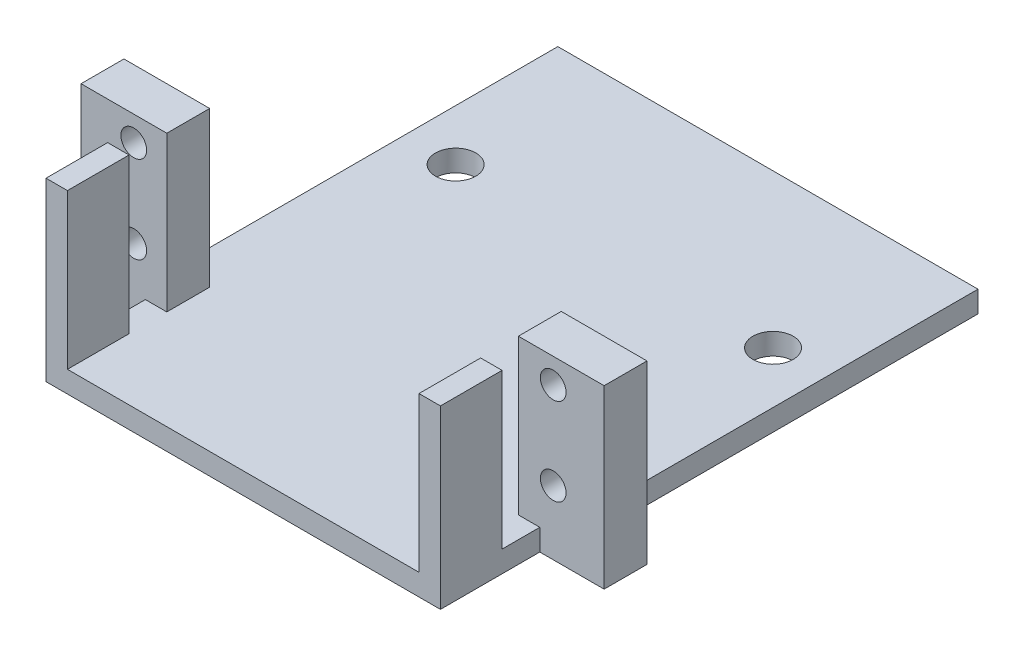
SolidWorks part; units mm, degrees
ref_plane "Front Plane" through (0, 0, 0) normal (0, 0, 1) x (1, 0, 0)
ref_plane "Top Plane" through (0, 0, 0) normal (0, 1, 0) x (1, 0, 0)
ref_plane "Right Plane" through (0, 0, 0) normal (1, 0, 0) x (0, 0, -1)
sketch "Sketch1" plane through (0, 0, 0) normal (0, 1, 0) x (1, 0, 0)
  line L1 (0, 0) -> (46, 0)
  line L2 (0, 0) -> (0, 36.614)
  line L3 (0, 36.614) -> (46, 36.614)
  line L4 (46, 0) -> (46, 36.614)
  dimension "D1" = 46
extrude "Boss-Extrude1" add sketch "Sketch1" along normal blind 2.5
sketch "Sketch2" plane through (0, 2.5, 0) normal (0, 1, 0) x (1, 0, 0)
  line L1 (0, 36.614) -> (2.5, 36.614)
  line L2 (0, 36.614) -> (0, 11.588)
  line L3 (0, 11.588) -> (2.5, 11.588)
  line L4 (2.5, 36.614) -> (2.5, 11.588)
  line L5 (0, 0) -> (2.5, 0)
  line L6 (0, 0) -> (0, 7.188)
  line L7 (0, 7.188) -> (2.5, 7.188)
  line L8 (2.5, 0) -> (2.5, 7.188)
  line L9 (46, 0) -> (43.5, 0)
  line L10 (46, 0) -> (46, 7.188)
  line L11 (46, 7.188) -> (43.5, 7.188)
  line L12 (43.5, 0) -> (43.5, 7.188)
  line L13 (46, 36.614) -> (43.5, 36.614)
  line L14 (46, 36.614) -> (46, 11.588)
  line L15 (46, 11.588) -> (43.5, 11.588)
  line L16 (43.5, 36.614) -> (43.5, 11.588)
  point P20 (44.75, 7.188)
  dimension "D1" = 2.5
  dimension "D2" = 2.5
  dimension "D3" = 2.5
  dimension "D4" = 2.5
  dimension "D5" = 7.188
  dimension "D6" = 4.4
  dimension "D7" = 7.188
  dimension "D8" = 4.4
extrude "Boss-Extrude2" add sketch "Sketch2" along normal blind 20.8351
sketch "Sketch4" plane through (0, 0, -11.588) normal (0, 0, 1) x (1, 0, 0)
  line L0 (2.5, 23.3351) -> (2.5, 2.5) construction
  line L1 (2.5, 20.5529) -> (-7.5, 20.5529)
  line L2 (2.5, 20.5529) -> (2.5, 0)
  line L3 (2.5, 0) -> (-7.5, 0)
  line L4 (-7.5, 20.5529) -> (-7.5, 0)
  line L5 (43.5, 23.3351) -> (43.5, 2.5) construction
  line L6 (43.5, 20.5529) -> (53.5, 20.5529)
  line L7 (43.5, 20.5529) -> (43.5, 0)
  line L8 (43.5, 0) -> (53.5, 0)
  line L9 (53.5, 20.5529) -> (53.5, 0)
  dimension "D1" = 10
  dimension "D2" = 10
extrude "Boss-Extrude8" add sketch "Sketch4" against normal blind 5
sketch "Sketch5" plane through (0, 0, 0) normal (-1, 0, 0) x (0, 0, 1)
  line L1 (-36.614, 23.3351) -> (-16.588, 23.3351)
  line L2 (-36.614, 23.3351) -> (-36.614, 0)
  line L3 (-36.614, 0) -> (-16.588, 0)
  line L4 (-16.588, 23.3351) -> (-16.588, 0)
extrude "Cut-Extrude1" cut sketch "Sketch5" against normal blind 100
sketch "Sketch6" plane through (0, 0, -16.588) normal (0, 0, -1) x (-1, 0, 0)
  line L0 (7.5, 0) -> (-53.5, 0) construction
  line L1 (-47.5, 2.5) -> (1.5, 2.5)
  line L2 (-47.5, 2.5) -> (-47.5, 0)
  line L3 (-47.5, 0) -> (1.5, 0)
  line L4 (1.5, 2.5) -> (1.5, 0)
  line L5 (-53.5, 0) -> (-53.5, 20.5529) construction
  line L6 (7.5, 20.5529) -> (7.5, 0) construction
  dimension "D1" = 2.5
  dimension "D2" = 6
  dimension "D3" = 6
extrude "Boss-Extrude9" add sketch "Sketch6" along normal blind 44.6018
sketch "Sketch7" plane through (0, 2.5, 0) normal (0, 1, 0) x (1, 0, 0)
  circle A0 centre (4.4582, 43.3138) radius 2.35
  circle A1 centre (41.4728, 43.3138) radius 2.35
  dimension "D1" = 4.7
  dimension "D2" = 4.7
extrude "Cut-Extrude2" cut sketch "Sketch7" against normal blind 57
sketch "Sketch8" plane through (0, 0, 0) normal (0, 0, 1) x (1, 0, 0)
sketch "Sketch9" plane through (0, 0, 0) normal (-1, 0, 0) x (0, 0, 1)
  line L1 (0, 23.3351) -> (-16.588, 23.3351)
  line L2 (0, 23.3351) -> (0, 20.5529)
  line L3 (0, 20.5529) -> (-16.588, 20.5529)
  line L4 (-16.588, 23.3351) -> (-16.588, 20.5529)
extrude "Cut-Extrude3" cut sketch "Sketch9" against normal blind 47
sketch "Sketch10" plane through (0, 0, -11.588) normal (0, 0, 1) x (1, 0, 0)
  circle A0 centre (-1.3535, 17.6577) radius 1.5
  circle A1 centre (-1.3535, 7.4923) radius 1.5
  circle A2 centre (47.5607, 17.6577) radius 1.5
  circle A3 centre (47.5607, 7.4923) radius 1.5
  point P8 (47.5607, 17.6577)
  point P9 (-1.3535, 7.4923)
  point P10 (48.3301, 17.6577)
  point P11 (47.6047, 7.5044)
  point P12 (47.5607, 7.4923)
  point P13 (48.3301, 17.6577)
  point P14 (-1.3535, 17.6577)
  dimension "D1" = 3
  dimension "D2" = 3
  dimension "D3" = 3
  dimension "D5" = 3
extrude "Cut-Extrude4" cut sketch "Sketch10" against normal blind 10
